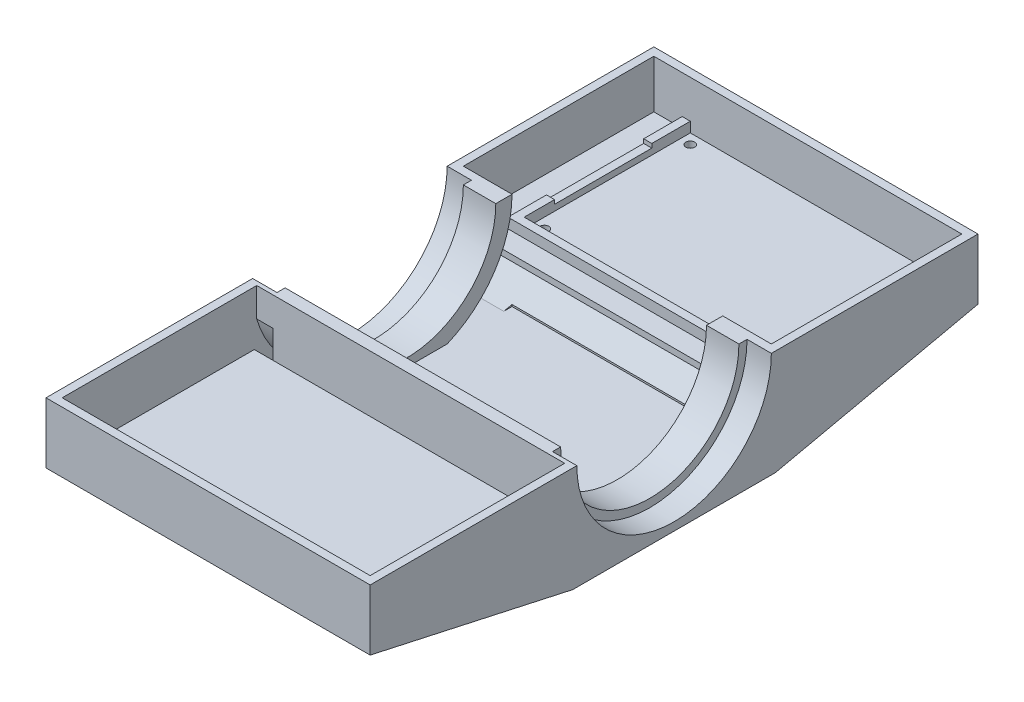
SolidWorks part; units mm, degrees
ref_plane "Спереди" through (0, 0, 0) normal (0, 0, 1) x (1, 0, 0)
ref_plane "Сверху" through (0, 0, 0) normal (0, 1, 0) x (1, 0, 0)
ref_plane "Справа" through (0, 0, 0) normal (1, 0, 0) x (0, 0, -1)
sketch "Эскиз1" plane through (0, 0, 0) normal (1, 0, 0) x (0, 0, -1)
  line L0 (-72.0575, 0) -> (82.2, 0) construction
  line L1 (0, 49.5774) -> (0, -46.7011) construction
  line L2 (-75, 0) -> (-75, -15)
  line L3 (-4.5637, -26) -> (25, -26)
  line L4 (-24, 0) -> (-75, 0)
  line L5 (24, 0) -> (75, 0)
  line L6 (25, -26) -> (75, -15)
  line L7 (75, -15) -> (75, 0)
  line L8 (-4.5637, -26) -> (-25, -26)
  line L9 (-25, -26) -> (-75, -15)
  arc A0 (-24, 0) -> (24, 0) centre (0, 0) ccw
  dimension "D1" = 24
  dimension "D2" = 29.5637
  dimension "D3" = 150
  dimension "D4" = 75
  dimension "D5" = 15
  dimension "D6" = 15
  dimension "D7" = 25
  dimension "D8" = 25
extrude "Бобышка-Вытянуть1" add sketch "Эскиз1" along normal blind 40 and the other way blind 40
sketch "Эскиз3" plane through (0, 0, 0) normal (1, 0, 0) x (0, 0, -1)
  line L0 (-24, 0) -> (-75, 0) construction
  line L1 (75, 0) -> (24, 0) construction
  line L2 (26, 0) -> (73, 0)
  line L3 (73, 0) -> (73, -13.3922)
  line L4 (73, -13.3922) -> (23.8787, -24)
  line L5 (23.8787, -24) -> (-24.7826, -24)
  line L6 (-24.7826, -24) -> (-73, -13.4006)
  line L7 (-73, -13.4006) -> (-73, 0)
  line L8 (-73, 0) -> (-26, 0)
  line L9 (-75, 0) -> (-75, -15) construction
  line L10 (25, -26) -> (75, -15) construction
  line L11 (-25, -26) -> (25, -26) construction
  line L12 (-75, -15) -> (-25, -26) construction
  line L13 (-26, 0) -> (26, 0)
  dimension "D2" = 2
  dimension "D3" = 2
  dimension "D4" = 2
  dimension "D5" = 2
  dimension "D6" = 2
extrude "Вырез-Вытянуть2" cut sketch "Эскиз3" against normal blind 34 and the other way blind 34
sketch "Эскиз7" plane through (0, 0, 0) normal (1, 0, 0) x (0, 0, -1)
  line L0 (-26.2, 0) -> (26.2, 0)
  line L1 (10.509, -24) -> (-10.509, -24)
  line L4 (-73, 0) -> (-73, -14.0428)
  line L5 (-73, -14.0428) -> (-24.7826, -24)
  line L6 (-24.7826, -24) -> (-10.509, -24)
  line L7 (-73, 0) -> (-26.2, 0)
  line L8 (26.2, 0) -> (73, 0)
  line L9 (73, 0) -> (73, -13.3922)
  line L10 (73, -13.3922) -> (23.9633, -24)
  line L11 (23.9633, -24) -> (10.509, -24)
extrude "Вырез-Вытянуть3" cut sketch "Эскиз7" against normal blind 38 and the other way blind 38
sketch "Эскиз8" plane through (-38, 0, 0) normal (1, 0, 0) x (0, 0, -1)
  line L1 (-24, 0) -> (-75, 0) construction
  line L2 (75, 0) -> (24, 0) construction
  line L3 (-26, 0) -> (-22, 0)
  line L4 (22, 0) -> (26, 0)
  arc A0 (-26, 0) -> (26, 0) centre (0, 0) ccw
  arc A1 (-22, 0) -> (22, 0) centre (0, 0) ccw
  dimension "D1" = 26
  dimension "D2" = 22
extrude "Бобышка-Вытянуть2" add sketch "Эскиз8" along normal blind 76
sketch "Эскиз9" plane through (38, 0, 0) normal (1, 0, 0) x (0, 0, -1)
  circle A0 centre (0, 0) radius 24
extrude "Вырез-Вытянуть4" cut sketch "Эскиз9" against normal blind 4
sketch "Эскиз10" plane through (-38, 0, 0) normal (-1, 0, 0) x (0, 0, 1)
  circle A0 centre (0, 0) radius 24
extrude "Вырез-Вытянуть5" cut sketch "Эскиз10" against normal blind 4
sketch "Эскиз11" plane through (0, 0, 0) normal (0, 1, 0) x (1, 0, 0)
  line L0 (38, 26) -> (-38, 26) construction
  line L1 (-26, 26) -> (26, 26)
  line L2 (-26, 26) -> (-26, -26)
  line L3 (-26, -26) -> (26, -26)
  line L4 (26, 26) -> (26, -26)
  line L5 (38, -26) -> (-38, -26) construction
  line L6 (40, 75) -> (40, 24) construction
  line L7 (-40, 75) -> (-40, 24) construction
  dimension "D1" = 0
  dimension "D2" = 0
  dimension "D3" = 52
  dimension "D4" = 14
  dimension "D5" = 14
extrude "Вырез-Вытянуть6" cut sketch "Эскиз11" against normal blind 24
sketch "Эскиз16" plane through (0, 0, 0) normal (0, 1, 0) x (1, 0, 0)
  line L0 (-38, -73) -> (-38, -24.7826) construction
  line L1 (-38, -25) -> (38, -25)
  line L2 (-38, -25) -> (-38, -27)
  line L3 (-38, -27) -> (38, -27)
  line L4 (38, -25) -> (38, -27)
  line L5 (38, -73) -> (38, -24.7826) construction
  line L6 (-26, -26) -> (-38, -26) construction
  dimension "D1" = 2
  dimension "D2" = 1
extrude "Вырез-Вытянуть8" cut sketch "Эскиз16" against normal blind 23.5
sketch "Эскиз17" plane through (-38, 0, 0) normal (1, 0, 0) x (0, 0, -1)
  line L0 (-75, 0) -> (-75, -15) construction
  line L1 (-73, -13.3922) -> (-25.5983, -13.3922)
  line L2 (-75, -15) -> (-25, -26) construction
  line L3 (-73, -14.8922) -> (-27.0983, -14.8922)
  line L4 (-27.0983, -14.8922) -> (-27.0983, -25.5384)
  line L5 (-27.0983, -25.5384) -> (-25.5983, -25.8684)
  line L6 (-25.5983, -25.8684) -> (-25.5983, -13.3922)
  line L7 (-73, -13.3922) -> (-73, -14.8922)
  dimension "D1" = 2
  dimension "D2" = 2
  dimension "D3" = 1.5
  dimension "D4" = 1.5
  dimension "D5" = 0
  dimension "D6" = 0
extrude "Бобышка-Вытянуть4" add sketch "Эскиз17" along normal blind 77.5
sketch "Эскиз19" plane through (0, 0, 0) normal (0, 1, 0) x (1, 0, 0)
  line L1 (-34, -22) -> (34, -22)
  line L2 (-34, -22) -> (-34, -25)
  line L3 (-26, -25) -> (-38, -25) construction
  line L4 (-34, -25) -> (34, -25)
  line L7 (38, -25) -> (26, -25) construction
  line L8 (34, -25) -> (34, -22)
extrude "Бобышка-Вытянуть6" add sketch "Эскиз19" against normal blind 27
sketch "Эскиз21" plane through (0, -30.0458, 6.6101) normal (0, -0.9766, 0.2149) x (1, 0, 0)
  line L0 (-40, 70.0254) -> (-40, 18.8297) construction
  line L1 (-38, 68.0254) -> (-24, 68.0254)
  line L2 (-38, 68.0254) -> (-38, 58.0254)
  line L3 (-38, 58.0254) -> (-24, 58.0254)
  line L4 (-24, 68.0254) -> (-24, 58.0254)
  line L5 (-40, 70.0254) -> (40, 70.0254) construction
  dimension "D1" = 14
  dimension "D2" = 10
  dimension "D3" = 2
  dimension "D4" = 2
extrude "Вырез-Вытянуть10" cut sketch "Эскиз21" against normal blind 2
sketch "Эскиз22" plane through (0, -13.3922, 0) normal (0, 1, 0) x (1, 0, 0)
  line L1 (-38, -73) -> (-24, -73)
  line L2 (-38, -73) -> (-38, -63)
  line L3 (-38, -63) -> (-24, -63)
  line L4 (-24, -73) -> (-24, -63)
  dimension "D1" = 14
  dimension "D2" = 10
extrude "Вырез-Вытянуть11" cut sketch "Эскиз22" against normal blind 6
sketch "Эскиз23" plane through (0, -14.8922, 0) normal (0, -1, 0) x (1, 0, 0)
  line L0 (-38, 63) -> (-24, 63)
  line L2 (-38, 63) -> (-38, 61.5)
  line L3 (-38, 61.5) -> (-22.5, 61.5)
  line L4 (-22.5, 64.1434) -> (-22.5, 61.5)
  line L5 (-24, 73.0467) -> (-22.5, 73.0467)
  line L6 (-24, 73.0467) -> (-24, 63)
  line L8 (-22.5, 73.0467) -> (-22.5, 64.1434)
  dimension "D1" = 1.5
  dimension "D2" = 1.5
extrude "Бобышка-Вытянуть7" add sketch "Эскиз23" along normal blind 1.4
sketch "Эскиз24" plane through (-22.5, 0, 0) normal (1, 0, 0) x (0, 0, -1)
  line L0 (-73.0467, -15.4297) -> (-69.1265, -16.2922)
  line L1 (-69.1265, -16.2922) -> (-73.0467, -16.2922)
  line L2 (-73.0467, -16.2922) -> (-73.0467, -15.4297)
extrude "Вырез-Вытянуть12" cut sketch "Эскиз24" against normal blind 3.4
sketch "Эскиз25" plane through (0, 0, 22) normal (0, 0, -1) x (-1, 0, 0)
  line L1 (-34, -27) -> (34, -27)
  line L2 (-34, -27) -> (-34, -26)
  line L3 (-34, -26) -> (34, -26)
  line L4 (34, -27) -> (34, -26)
extrude "Вырез-Вытянуть13" cut sketch "Эскиз25" against normal blind 3.4
sketch "Эскиз26" plane through (38, 0, 0) normal (-1, 0, 0) x (0, 0, 1)
  line L0 (-73, -11.8922) -> (-25, -11.8922)
  line L1 (-25, -11.8922) -> (-25, -13.3922)
  line L2 (-25, -13.3922) -> (-73, -13.3922)
  line L3 (-73, -13.3922) -> (-73, -11.8922)
  line L4 (-25, -26) -> (-75, -15) construction
  dimension "D1" = 1.5
  dimension "D2" = 2
  dimension "D3" = 2
  dimension "D4" = 50
extrude "Бобышка-Вытянуть8" add sketch "Эскиз26" along normal blind 78
sketch "Эскиз27" plane through (0, -11.8922, 0) normal (0, 1, 0) x (1, 0, 0)
  line L0 (40, 75) -> (40, 24) construction
  line L1 (-31, 75) -> (40, 75)
  line L2 (-31, 75) -> (-31, 30)
  line L3 (-31, 30) -> (40, 30)
  line L4 (40, 75) -> (40, 30)
  line L5 (-29, 73) -> (38, 73)
  line L6 (-29, 73) -> (-29, 32)
  line L7 (-29, 32) -> (38, 32)
  line L8 (38, 73) -> (38, 32)
  line L9 (38, 73) -> (-38, 73) construction
  dimension "D1" = 41
  dimension "D2" = 67
  dimension "D3" = 2
  dimension "D4" = 2
  dimension "D5" = 2
  dimension "D6" = 2
  dimension "D7" = 0
  dimension "D8" = 0
extrude "Бобышка-Вытянуть9" add sketch "Эскиз27" along normal blind 2.5
sketch "Эскиз28" plane through (0, -11.8922, 0) normal (0, 1, 0) x (1, 0, 0)
  line L0 (38, 73) -> (38, 26) construction
  line L1 (-29, 32) -> (38, 32) construction
  line L2 (-29, 73) -> (38, 73) construction
  line L3 (-29, 73) -> (-29, 32) construction
  line L4 (-29, 32) -> (38, 32) construction
  line L5 (-29, 73) -> (-29, 32) construction
  circle A0 centre (-26.5, 70.5) radius 1.1
  circle A1 centre (-26.5, 34.5) radius 1.1
  circle A2 centre (35.5, 70.5) radius 1.1
  circle A3 centre (35.5, 34.5) radius 1.1
  dimension "D1" = 2.2
  dimension "D2" = 2.2
  dimension "D3" = 2.2
  dimension "D4" = 2.2
  dimension "D5" = 2.5
  dimension "D6" = 2.5
  dimension "D7" = 2.5
  dimension "D8" = 2.5
  dimension "D9" = 2.5
  dimension "D10" = 2.5
  dimension "D11" = 2.5
  dimension "D12" = 2.5
extrude "Вырез-Вытянуть14" cut sketch "Эскиз28" against normal blind 2
sketch "Эскиз29" plane through (0, -9.3922, 0) normal (0, 1, 0) x (1, 0, 0)
  line L0 (-31, 73) -> (-31, 30) construction
  line L1 (-31, 63.5) -> (-29, 63.5)
  line L2 (-31, 63.5) -> (-31, 39.5)
  line L3 (-31, 39.5) -> (-29, 39.5)
  line L4 (-29, 63.5) -> (-29, 39.5)
  line L5 (-29, 73) -> (-29, 32) construction
  dimension "D1" = 24
  dimension "D2" = 9.5
  dimension "D3" = 9.5
extrude "Вырез-Вытянуть15" cut sketch "Эскиз29" against normal blind 1
